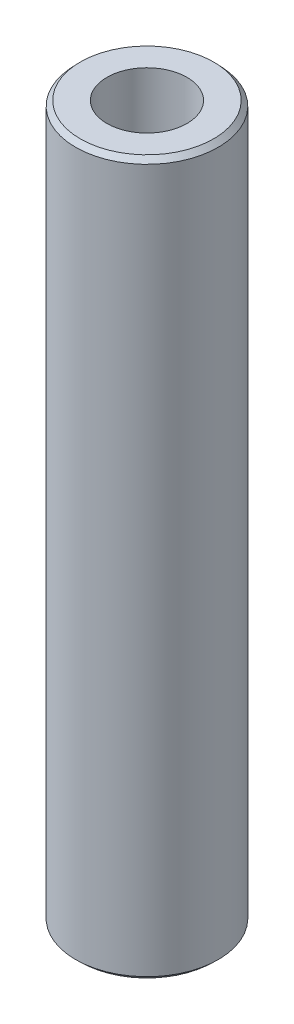
SolidWorks part; units mm, degrees
ref_plane "Front Plane" through (0, 0, 0) normal (0, 0, 1) x (1, 0, 0)
ref_plane "Top Plane" through (0, 0, 0) normal (0, 1, 0) x (1, 0, 0)
ref_plane "Right Plane" through (0, 0, 0) normal (1, 0, 0) x (0, 0, -1)
sketch "Sketch1" plane through (0, 0, 0) normal (0, 1, 0) x (1, 0, 0)
  circle A0 centre (0, 0) radius 60
  dimension "SHAFT_OD" = 120
extrude "Boss-Extrude1" add sketch "Sketch1" along normal blind 600
sketch "Sketch2" plane through (0, 0, 0) normal (0, 1, 0) x (1, 0, 0)
  circle A0 centre (0, 0) radius 33.696
  dimension "BORE_D" = 67.392
extrude "Cut-Extrude1" cut sketch "Sketch2" along normal through all
chamfer "Chamfer1" distance 4.17 angle 43.27 2 edges at (0, 600, 60) (0, 0, 60) first distance on face at (0, 600, 60) first distance on face at (0, 0, 33.696)
